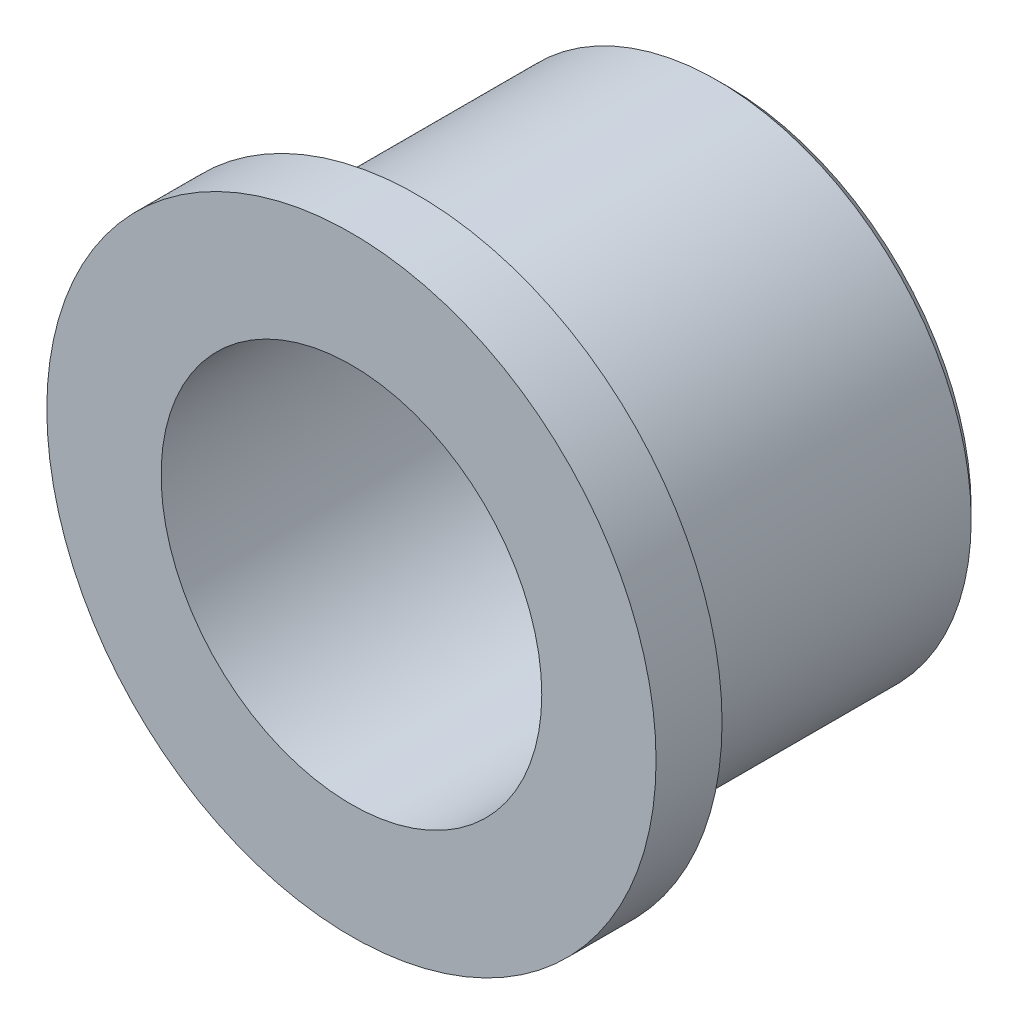
SolidWorks part; units mm, degrees
ref_plane "Front Plane" through (0, 0, 0) normal (0, 0, 1) x (1, 0, 0)
ref_plane "Top Plane" through (0, 0, 0) normal (0, 1, 0) x (1, 0, 0)
ref_plane "Right Plane" through (0, 0, 0) normal (1, 0, 0) x (0, 0, -1)
ref_axis "X-axis" through (-88.99, 0, 0) along (1, 0, 0)
ref_axis "Y-axis" through (0, 55, 0) along (0, -1, 0)
ref_axis "Z-axis" through (0, 0, -88.99) along (0, 0, 1)
sketch "Sketch2" plane through (0, 0, 0) normal (1, 0, 0) x (0, 0, -1)
  line L0 (0, 0) -> (20.8026, 0) construction
  line L1 (0, 0) -> (-18.8214, 0)
  line L2 (-18.8214, 0) -> (-18.8214, 15.2442)
  line L3 (-18.8214, 15.2442) -> (-15.5194, 15.2442)
  line L4 (-15.5194, 15.2442) -> (-15.5194, 12.7)
  line L5 (-15.5194, 12.7) -> (0, 12.7)
  line L6 (0, 12.7) -> (0, 0)
  dimension "D1" = 3.302
  dimension "D2" = 25.4
  dimension "D3" = 30.4885
revolve "Revolve2" add sketch "Sketch2" angle 360 about L0
hole_wizard "1/4 (0.75) Diameter Hole1" positions "Sketch3" profile "Sketch4" hole size "1/4" standard "ANSI Inch" end condition through all
sketch "Sketch3" plane through (0, 0, 18.8214) normal (0, 0, 1) x (1, 0, 0)
  point P0 (0, 0)
sketch "Sketch4" plane through (0, 0, 18.8214) normal (1, 0, 0) x (0, -1, 0)
  line L0 (0, 0) -> (0, 18.8214)
  line L1 (0, 18.8214) -> (9.525, 18.8214)
  line L2 (9.525, 18.8214) -> (9.525, 0)
  line L5 (9.525, 0) -> (0, 0)
  line L11 (0, -6.35) -> (0, 107.95) construction
  dimension "Thru Hole Dia." = 19.05
  dimension "Thru Hole Depth" = 18.8214
chamfer "Chamfer2" distance 0.508 angle 45 1 edges at (12.7, 0, 0)
